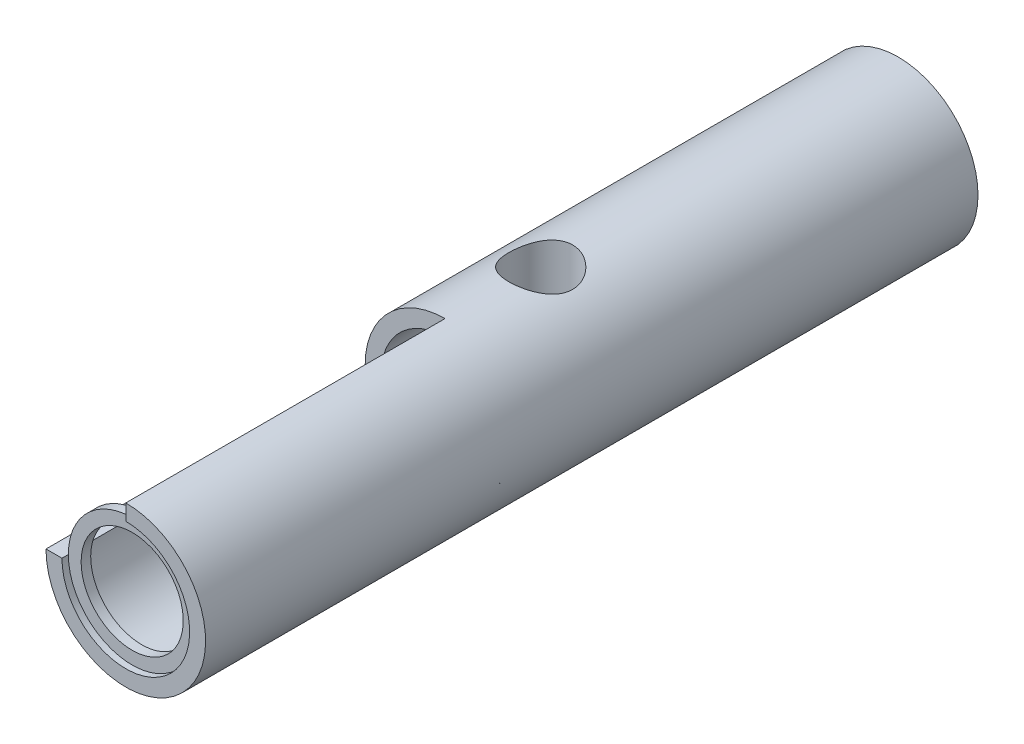
SolidWorks part; units mm, degrees
ref_plane "Face" through (0, 0, 0) normal (0, 0, 1) x (1, 0, 0)
ref_plane "Dessus" through (0, 0, 0) normal (0, 1, 0) x (1, 0, 0)
ref_plane "Droite" through (0, 0, 0) normal (1, 0, 0) x (0, 0, -1)
sketch "Esquisse1" plane through (0, 0, 0) normal (0, 0, 1) x (1, 0, 0)
  circle A0 centre (0, 0) radius 12.5
  dimension "D1" = 25
extrude "Base-Extrusion" add sketch "Esquisse1" along normal blind 121
sketch "Esquisse2" plane through (0, 0, 121) normal (0, 0, 1) x (1, 0, 0)
  circle A0 centre (0, 0) radius 10
  dimension "D1" = 20
extrude "Enlèv. mat.-Extru.1" cut sketch "Esquisse2" against normal blind 58
sketch "Esquisse3" plane through (0, 0, 63) normal (0, 0, 1) x (1, 0, 0)
  circle A0 centre (0, 0) radius 4
  dimension "D1" = 8
extrude "Enlèv. mat.-Extru.2" cut sketch "Esquisse3" against normal through all
sketch "Esquisse4" plane through (0, 0, 0) normal (0, 1, 0) x (-1, 0, 0)
  line L0 (0, 121) -> (0, 0) construction
  line L1 (12.5, 121) -> (-12.5, 121) construction
  line L2 (12.5, 121) -> (-12.5, 121) construction
  circle A0 centre (0, 56) radius 5
  dimension "D1" = 10
  dimension "D2" = 65
extrude "Enlèv. mat.-Extru.3" cut sketch "Esquisse4" against normal blind 8 and the other way blind 15
sketch "Esquisse5" plane through (0, -8, 0) normal (0, 1, 0) x (-1, 0, 0)
  line L0 (0, 121) -> (0, 0) construction
  circle A0 centre (0, 56) radius 3
  circle A1 centre (0, 56) radius 5 construction
  dimension "D1" = 6
extrude "Enlèv. mat.-Extru.4" cut sketch "Esquisse5" against normal through all
sketch "Esquisse6" plane through (0, 0, 0) normal (1, 0, 0) x (0, 0, -1)
  line L0 (-120, 10) -> (-120, 8)
  line L1 (-63, 10) -> (-121, 10) construction
  line L2 (-120, 8) -> (-118.5, 8)
  line L3 (-118.5, 8) -> (-118.5, 10)
  line L4 (-118.5, 10) -> (-120, 10)
  line L5 (-121, 12.5) -> (-121, -12.5) construction
  line L6 (6.277, 0) -> (-142.3906, 0) construction
  line L7 (-59, 0) -> (-63, 0) construction
  dimension "D1" = 1
  dimension "D2" = 1.5
  dimension "D3" = 8
  dimension "D4" = 10
ref_axis "Axe1" through (0, 0, 13) along (0, 0, 1)
sketch "Esquisse9" plane through (0, 0, 0) normal (1, 0, 0) x (0, 0, -1)
  line L0 (-13, 0) -> (-263, 0) construction
  line L1 (-71, 0) -> (-126, 0)
  line L2 (-71, 0) -> (-71, 32.3377)
  line L3 (-71, 32.3377) -> (-126, 32.3377)
  line L4 (-126, 0) -> (-126, 32.3377)
  line L5 (-121, 12.5) -> (-121, -12.5) construction
  line L6 (-121, 12.5) -> (-121, -12.5) construction
  dimension "D1" = 50
  dimension "D2" = 5
extrude "Enlèv. mat.-Extru.6" cut sketch "Esquisse9" against normal through all
revolve "Anneau élastique" add sketch "Esquisse6" angle 360 about L6
ref_plane "Plan1" through (0, 0, 69.4973) normal (0, 0, -1) x (-1, 0, 0)
sketch "Esquisse10" plane through (0, 0, 69.4973) normal (0, 0, -1) x (-1, 0, 0)
  point P0 (0, 0)
ref_plane "Plan2" through (0, 0, 97.5002) normal (0, 0, 1) x (1, 0, 0)
sketch "Esquisse11" plane through (0, 0, 97.5002) normal (0, 0, 1) x (1, 0, 0)
  point P0 (0, 0)
